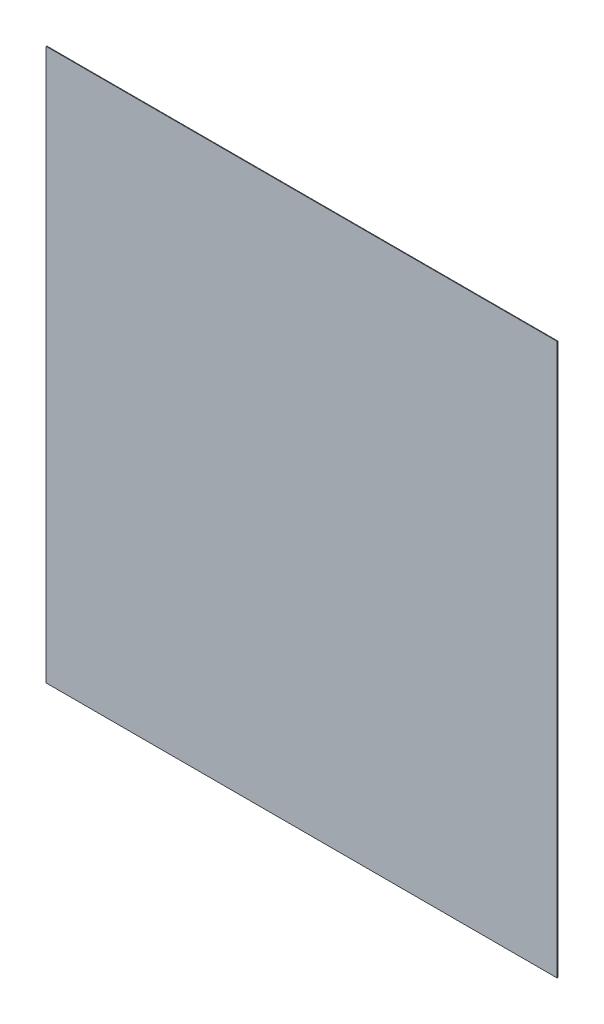
SolidWorks part; units mm, degrees
ref_plane "Front Plane" through (0, 0, 0) normal (0, 0, 1) x (1, 0, 0)
ref_plane "Top Plane" through (0, 0, 0) normal (0, 1, 0) x (1, 0, 0)
ref_plane "Right Plane" through (0, 0, 0) normal (1, 0, 0) x (0, 0, -1)
other "Configuration Table"
sketch "Sketch1" plane through (0, 0, 0) normal (0, 0, 1) x (1, 0, 0)
  line L1 (0, 0) -> (12000, 0)
  line L2 (0, 0) -> (0, 12950)
  line L3 (0, 12950) -> (12000, 12950)
  line L4 (12000, 0) -> (12000, 12950)
  dimension "D1" = 12000
  dimension "D2" = 12950
sheet metal parameters "Sheet-Metal1" thickness 15 parameters "D1"=0.7366
base flange "Base-Flange1" sketch "Sketch1" thickness 15 reverse thickness direction yes parameters "D1"=0.7366
flat pattern "Flat-Pattern1" [suppressed]
sketch "Bend-Lines1" plane through (0, 0, 0) normal (0, 1, 0) x (-1, 0, 0)
